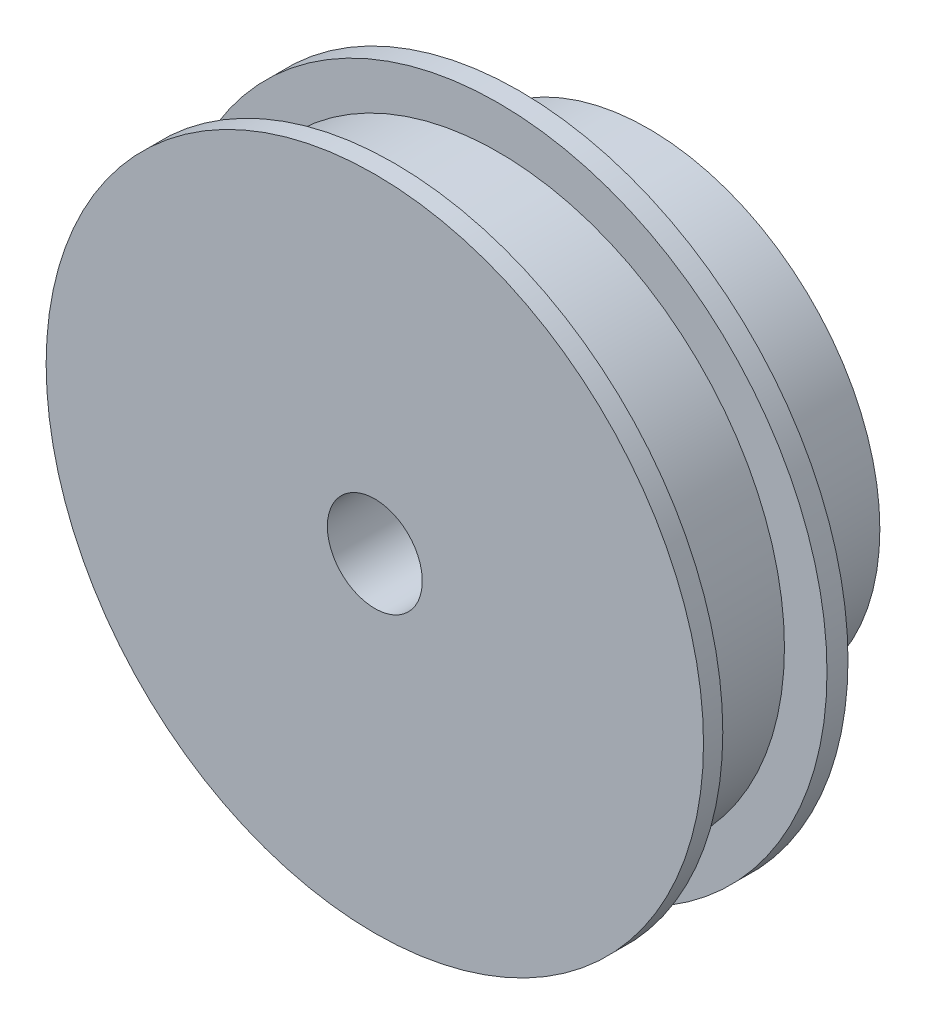
SolidWorks part; units mm, degrees
ref_plane "Front Plane" through (0, 0, 0) normal (0, 0, 1) x (1, 0, 0)
ref_plane "Top Plane" through (0, 0, 0) normal (0, 1, 0) x (1, 0, 0)
ref_plane "Right Plane" through (0, 0, 0) normal (1, 0, 0) x (0, 0, -1)
sketch "Sketch1" plane through (0, 0, 0) normal (0, 0, 1) x (1, 0, 0)
  circle A0 centre (0, 0) radius 15.5385
  dimension "D1" = 31.0769
extrude "Boss-Extrude1" add sketch "Sketch1" against normal blind 8.6741
sketch "Sketch2" plane through (0, 0, 0) normal (0, 0, 1) x (1, 0, 0)
  circle A0 centre (0, 0) radius 22.0726
  dimension "D1" = 44.1452
extrude "Boss-Extrude2" add sketch "Sketch2" along normal blind 1.4097
sketch "Sketch3" plane through (0, 0, 1.4097) normal (0, 0, 1) x (1, 0, 0)
  circle A0 centre (0, 0) radius 19.2151
  dimension "D1" = 38.4302
extrude "Boss-Extrude3" add sketch "Sketch3" along normal blind 6.9977
ref_plane "Plane1" through (0, 0, 8.4074) normal (0, 0, 1) x (1, 0, 0)
extrude "Boss-Extrude5" add sketch "Sketch2<3>" along normal blind 1.2954 from surface starting at plane "Plane1"
sketch "Sketch2<3>" plane through (0, 0, 0) normal (0, 0, 1) x (1, 0, 0) same geometry as "Sketch2"
sketch "Sketch5" plane through (0, 0, -8.6741) normal (0, 0, -1) x (-1, 0, 0)
  circle A0 centre (0, 0) radius 3.1877
  dimension "D1" = 6.3754
extrude "Cut-Extrude1" cut sketch "Sketch5" against normal through all
